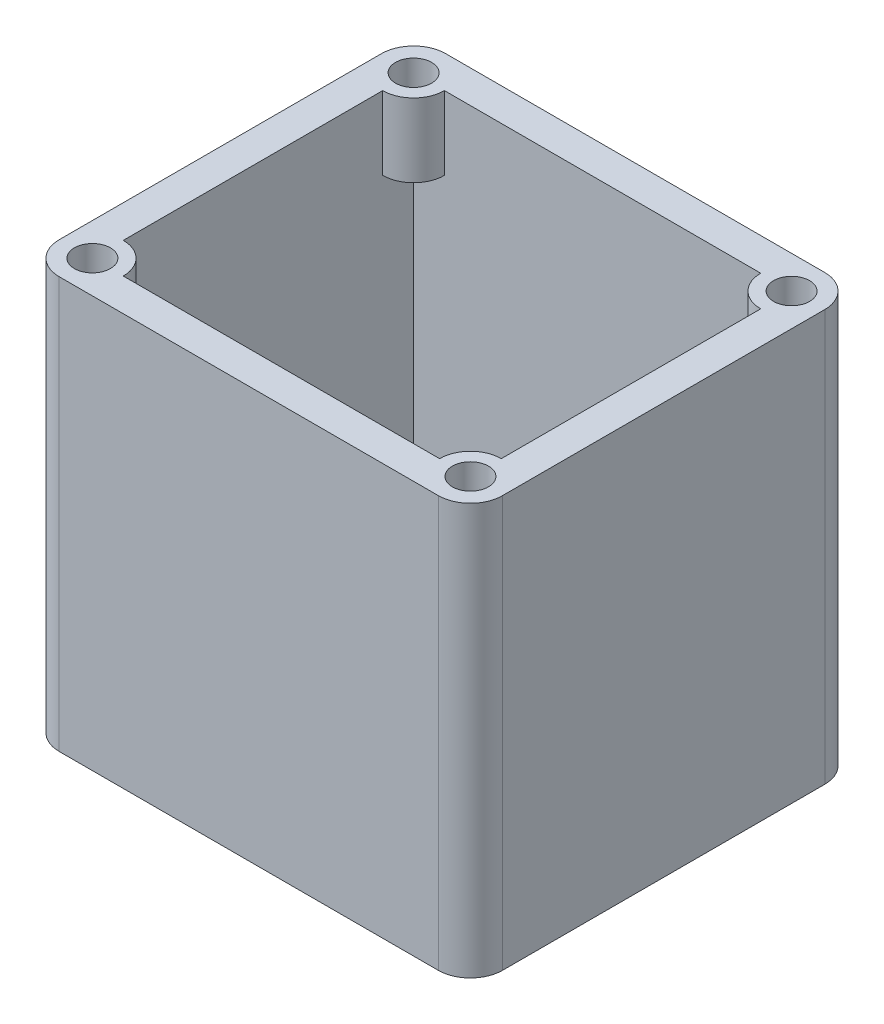
SolidWorks part; units mm, degrees
ref_plane "Front Plane" through (0, 0, 0) normal (0, 0, 1) x (1, 0, 0)
ref_plane "Top Plane" through (0, 0, 0) normal (0, 1, 0) x (1, 0, 0)
ref_plane "Right Plane" through (0, 0, 0) normal (1, 0, 0) x (0, 0, -1)
sketch "Sketch1" plane through (0, 0, 0) normal (0, 1, 0) x (1, 0, 0)
  line L1 (-34.505, -30.08) -> (34.505, -30.08)
  line L2 (-34.505, -30.08) -> (-34.505, 30.08)
  line L3 (-34.505, 30.08) -> (34.505, 30.08)
  line L4 (34.505, -30.08) -> (34.505, 30.08)
  line L5 (-34.505, -30.08) -> (34.505, 30.08) construction
  line L6 (-34.505, 30.08) -> (34.505, -30.08) construction
  point P0 (0, 0)
  dimension "Outer Box Length" = 69.01
  dimension "Outer Box Width" = 60.16
extrude "Boss-Extrude3" add sketch "Sketch1" along normal blind 64.008 contours L3 L4 L1 L2
sketch "Sketch2" plane through (0, 64.008, 0) normal (0, 1, 0) x (1, 0, 0)
  line L0 (-34.505, 30.08) -> (34.505, 30.08) construction
  line L1 (29.425, -25) -> (-29.425, -25)
  line L2 (29.425, -25) -> (29.425, 25)
  line L3 (29.425, 25) -> (-29.425, 25)
  line L4 (-29.425, -25) -> (-29.425, 25)
  line L5 (29.425, -25) -> (-29.425, 25) construction
  line L6 (29.425, 25) -> (-29.425, -25) construction
  line L7 (-34.505, -30.08) -> (-34.505, 30.08) construction
  point P0 (0, 0)
  dimension "D1" = 5.08
  dimension "D2" = 5.08
extrude "Cut-Extrude4" cut sketch "Sketch2" against normal blind 58.928 contours L4 L3 L2 L1
fillet "Fillet1" radius 5 4 edges at (34.505, 32.004, -30.08) (-34.505, 32.004, -30.08) (-34.505, 32.004, 30.08) (34.505, 32.004, 30.08)
sketch "Sketch3" plane through (0, 64.008, 0) normal (0, 1, 0) x (1, 0, 0)
  circle A0 centre (-29.425, 25) radius 4.8067
  circle A2 centre (29.425, 25) radius 4.8067
  circle A3 centre (-29.425, -25) radius 4.8067
  circle A4 centre (29.425, -25) radius 4.8067
  circle A5 centre (-29.425, 25) radius 2.8067
  circle A6 centre (29.425, 25) radius 2.8067
  circle A7 centre (29.425, -25) radius 2.8067
  circle A8 centre (-29.425, -25) radius 2.8067
  dimension "D1" = 9.6134
extrude "Boss-Extrude4" add sketch "Sketch3" against normal blind 11.43 contours A2 | A0 | A3 | A4
extrude "Cut-Extrude5" cut sketch "Sketch3<3>" against normal blind 6.35 contours A5 | A8 | A7 | A6
sketch "Sketch3<3>" plane through (0, 64.008, 0) normal (0, 1, 0) x (1, 0, 0) same geometry as "Sketch3"
sketch "Sketch9" plane through (0, 5.08, 0) normal (0, 1, 0) x (1, 0, 0)
  line L0 (-29.425, -20.1933) -> (-29.425, 20.1933) construction
  line L1 (29.425, 25) -> (-29.425, 25) construction
  line L2 (29.425, -25) -> (29.425, 25) construction
  line L3 (29.425, -25) -> (-29.425, -25) construction
  line L4 (-29.425, -25) -> (-29.425, 25) construction
  circle A0 centre (-23.225, 18.85) radius 4.8067
  circle A1 centre (23.525, 19.1) radius 4.8067
  circle A2 centre (23.275, -19.05) radius 4.8067
  circle A3 centre (-23.475, -19.05) radius 4.8067
  circle A4 centre (-23.475, -19.05) radius 2.8067
  circle A5 centre (23.275, -19.05) radius 2.8067
  circle A6 centre (23.525, 19.1) radius 2.8067
  circle A7 centre (-23.225, 18.85) radius 2.8067
  dimension "D3" = 9.6134
  dimension "D1" = 6.2
  dimension "D2" = 6.15
  dimension "D4" = 5.9
  dimension "D5" = 5.9
  dimension "D6" = 6.15
  dimension "D7" = 5.95
  dimension "D8" = 5.95
  dimension "D9" = 5.95
  dimension "D10" = 2
extrude "Boss-Extrude5" add sketch "Sketch9" along normal blind 6.35
sketch "Sketch10" plane through (0, 5.08, 0) normal (0, 1, 0) x (1, 0, 0)
  line L1 (-14.2125, -12) -> (14.2125, -12)
  line L2 (-14.2125, -12) -> (-14.2125, 12)
  line L3 (-14.2125, 12) -> (14.2125, 12)
  line L4 (14.2125, -12) -> (14.2125, 12)
  line L5 (-14.2125, -12) -> (14.2125, 12) construction
  line L6 (-14.2125, 12) -> (14.2125, -12) construction
  circle A0 centre (14.2125, 12) radius 2.159
  circle A1 centre (14.2125, -12) radius 2.159
  circle A2 centre (-14.2125, 12) radius 2.159
  circle A3 centre (-14.2125, -12) radius 2.159
  point P0 (0, 0)
  dimension "D3" = 4.318
  dimension "D1" = 28.425
  dimension "D2" = 24
extrude "Cut-Extrude6" cut sketch "Sketch10" against normal up to surface (5.08 mm away) contours A0 | A1 | A3 | A2 up to face at (0, 0, 0)
sketch "Sketch12" plane through (0, 5.08, 0) normal (0, 1, 0) x (1, 0, 0)
  line L0 (-29.425, -25) -> (-29.425, 25) construction
  circle A0 centre (-23.225, 18.85) radius 4.8067 construction
  text T0 "1"
  dimension "D1" = 2
  dimension "D2" = 10
extrude "Boss-Extrude6" add sketch "Sketch12" along normal blind 1
sketch "Face 1 Connector Holes" plane through (-34.505, 0, 0) normal (-1, 0, 0) x (0, 0, 1)
  line L0 (-25.08, 64.008) -> (-25.08, 0) construction
  line L1 (-25.08, 63.83) -> (25.08, 63.83)
  line L2 (-25.08, 63.83) -> (-25.08, 13.03)
  line L3 (-25.08, 13.03) -> (25.08, 13.03)
  line L4 (25.08, 63.83) -> (25.08, 13.03)
  line L5 (25.08, 0) -> (25.08, 64.008) construction
  line L6 (25.08, 0) -> (-25.08, 0) construction
  dimension "D1" = 50.8
  dimension "D2" = 13.03
sketch "Face 2 Connector Holes" plane through (0, 0, -30.08) normal (0, 0, -1) x (-1, 0, 0)
  line L0 (29.505, 0) -> (29.505, 64.008) construction
  line L1 (29.505, 13.03) -> (-29.505, 13.03)
  line L2 (29.505, 13.03) -> (29.505, 63.83)
  line L3 (29.505, 63.83) -> (-29.505, 63.83)
  line L4 (-29.505, 13.03) -> (-29.505, 63.83)
  line L5 (-29.505, 64.008) -> (-29.505, 0) construction
  line L6 (29.505, 0) -> (-29.505, 0) construction
  line L8 (18.105, 13.03) -> (11.705, 13.03)
  line L9 (18.105, 13.03) -> (18.105, 18.03)
  line L10 (18.105, 18.03) -> (11.705, 18.03)
  line L11 (11.705, 13.03) -> (11.705, 18.03)
  line L12 (-8.195, 13.03) -> (-18.595, 13.03)
  line L13 (-8.195, 13.03) -> (-8.195, 18.03)
  line L14 (-8.195, 18.03) -> (-18.595, 18.03)
  line L15 (-18.595, 13.03) -> (-18.595, 18.03)
  dimension "D1" = 13.03
  dimension "D2" = 50.8
  dimension "D3" = 11.4
  dimension "D4" = 6.4
  dimension "D5" = 5
  dimension "D6" = 37.7
  dimension "D7" = 10.4
  dimension "D8" = 5
sketch "Face 3 Connector Holes" plane through (34.505, 0, 0) normal (1, 0, 0) x (0, 0, -1)
  line L0 (-25.08, 64.008) -> (-25.08, 0) construction
  line L1 (-25.08, 63.83) -> (25.08, 63.83)
  line L2 (-25.08, 63.83) -> (-25.08, 13.03)
  line L3 (-25.08, 13.03) -> (25.08, 13.03)
  line L4 (25.08, 63.83) -> (25.08, 13.03)
  line L5 (25.08, 0) -> (25.08, 64.008) construction
  line L6 (-25.08, 0) -> (25.08, 0) construction
  line L8 (7.63, 13.03) -> (14.03, 13.03)
  line L9 (7.63, 13.03) -> (7.63, 18.03)
  line L10 (7.63, 18.03) -> (14.03, 18.03)
  line L11 (14.03, 13.03) -> (14.03, 18.03)
  dimension "D4" = 6.4
  dimension "D5" = 5
  dimension "D1" = 50.8
  dimension "D2" = 13.03
  dimension "D3" = 11.05
sketch "Face 4 Connector Holes" plane through (0, 0, 30.08) normal (0, 0, 1) x (1, 0, 0)
  line L0 (-29.505, 64.008) -> (-29.505, 0) construction
  line L1 (-29.505, 63.83) -> (29.505, 63.83)
  line L2 (-29.505, 63.83) -> (-29.505, 13.03)
  line L3 (-29.505, 13.03) -> (29.505, 13.03)
  line L4 (29.505, 63.83) -> (29.505, 13.03)
  line L5 (29.505, 0) -> (29.505, 64.008) construction
  line L6 (-29.505, 0) -> (29.505, 0) construction
  line L8 (-17.395, 13.03) -> (17.305, 13.03)
  line L9 (-17.395, 13.03) -> (-17.395, 18.03)
  line L10 (-17.395, 18.03) -> (17.305, 18.03)
  line L11 (17.305, 13.03) -> (17.305, 18.03)
  dimension "D1" = 50.8
  dimension "D2" = 13.03
  dimension "D3" = 34.7
  dimension "D4" = 5
  dimension "D5" = 12.2
equation "\"PCB Length\"= 56.85mm"
equation "\"PCB Width\"= 48mm"
equation "\"PCB Height\"= 2in"
equation "\"Insert Height\"= 0.25in"
equation "\"Wall Thickness\"= 0.2in"
equation "\"Support Hole OD\"= 0.17in"
equation "\"PCB Margin\"= 1mm"
equation "\"Screw Length\"= 7in / 16"
equation "\"Insert OD Size\"= 0.221in"
equation "\"PCB d1\"= 5.2mm"
equation "\"PCB d2\"= 5.15mm"
equation "\"PCB d3\"= 4.9mm"
equation "\"PCB d4\"= 4.9mm"
equation "\"PCB d5\"= 5.15mm"
equation "\"PCB d6\"= 4.95mm"
equation "\"PCB d7\"= 4.95mm"
equation "\"PCB d8\"= 4.95mm"
equation "\"Insert Wall Thickness\"= 2mm"
equation "\"PCB Underside Washer\"= 0.07in"
equation "\"Outer Box Length@Sketch1\" = 2 * \"Wall Thickness\" + 2 * \"PCB Margin\" + \"PCB Length\""
equation "\"Outer Box Width@Sketch1\"=2 * \"Wall Thickness\" + 2 * \"PCB Margin\" + \"PCB Width\""
equation "\"D1@Boss-Extrude3\"=\"Wall Thickness\"+\"Insert Height\"+\"PCB Underside Washer\"+\"PCB Height\""
equation "\"D2@Sketch2\"=\"Wall Thickness\""
equation "\"D1@Sketch2\"=\"Wall Thickness\""
equation "\"D1@Cut-Extrude4\"=\"PCB Height\"+\"PCB Underside Washer\"+\"Insert Height\""
equation "\"D1@Sketch3\"=\"Insert OD Size\"+ 2 * \"Insert Wall Thickness\""
equation "\"D1@Boss-Extrude4\"=\"Insert Height\"+ \"Wall Thickness\""
equation "\"D1@Cut-Extrude5\"=\"Insert Height\""
equation "\"D1@Sketch9\"=\"PCB d1\" + \"PCB Margin\""
equation "\"D4@Sketch9\"=\"PCB d3\"+\"PCB Margin\""
equation "\"D5@Sketch9\"=\"PCB d4\"+\"PCB Margin\""
equation "\"D6@Sketch9\"=\"PCB d5\" + \"PCB Margin\""
equation "\"D2@Sketch9\"=\"PCB d2\" + \"PCB Margin\" "
equation "\"D7@Sketch9\"=\"PCB d6\"+\"PCB Margin\""
equation "\"D8@Sketch9\"= \"PCB d8\"+\"PCB Margin\""
equation "\"D9@Sketch9\"=\"PCB d7\"+\"PCB Margin\""
equation "\"D10@Sketch9\"=\"Insert Wall Thickness\""
equation "\"D1@Boss-Extrude5\"=\"Insert Height\""
equation "\"D1@Sketch10\"=\"PCB Length\"/2"
equation "\"D2@Sketch10\"=\"PCB Width\"/2"
equation "\"D3@Sketch10\"=\"Support Hole OD\""
equation "\"D3@Sketch9\"=\"Insert OD Size\" + 2 * \"Insert Wall Thickness\""
equation "\"D1@Face 2 Connector Holes\"=\"Wall Thickness\" + \"Insert Height\"+1.6mm"
equation "\"D2@Face 2 Connector Holes\" = \"PCB Height\""
equation "\"D1@Face 1 Connector Holes\" = \"PCB Height\""
equation "\"D2@Face 1 Connector Holes\"=\"Wall Thickness\" +\"Insert Height\"+ 1.6mm"
equation "\"D1@Face 3 Connector Holes\" = \"PCB Height\""
equation "\"D2@Face 3 Connector Holes\"=\"Wall Thickness\" +\"Insert Height\"+ 1.6mm"
equation "\"D1@Face 4 Connector Holes\" = \"PCB Height\""
equation "\"D2@Face 4 Connector Holes\"=\"Wall Thickness\" +\"Insert Height\"+ 1.6mm"
equation "\"D6@Face 2 Connector Holes\"=36.7mm + \"PCB Margin\""
equation "\"D3@Face 2 Connector Holes\"=10.4mm + \"PCB Margin\""
equation "\"D3@Face 3 Connector Holes\"=10.05mm + \"PCB Margin\""
equation "\"D5@Face 4 Connector Holes\"=11.2mm + \"PCB Margin\""
equation "\"Head Height\" = 0.115in"
equation "\"Head Diameter\" = 0.322in"
